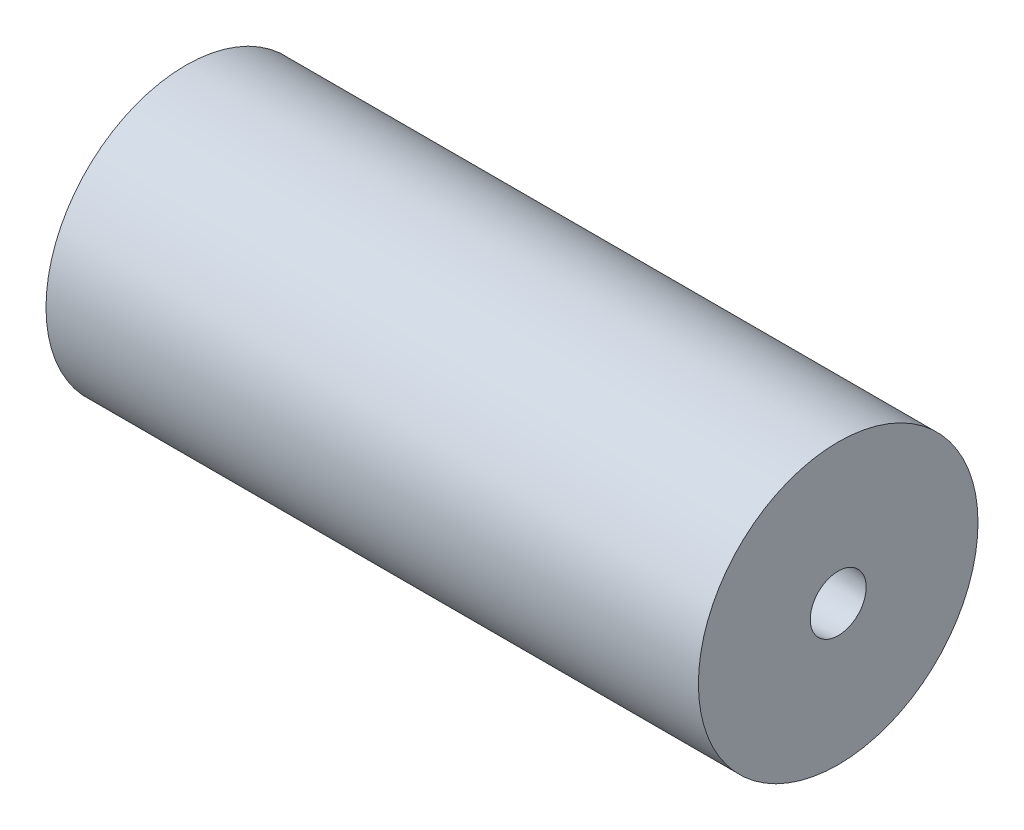
SolidWorks part; units mm, degrees
ref_plane "Front Plane" through (0, 0, 0) normal (0, 0, 1) x (1, 0, 0)
ref_plane "Top Plane" through (0, 0, 0) normal (0, 1, 0) x (1, 0, 0)
ref_plane "Right Plane" through (0, 0, 0) normal (1, 0, 0) x (0, 0, -1)
sketch "Sketch1" plane through (0, 0, 0) normal (0, 0, 1) x (1, 0, 0)
  line L0 (-22.225, 9.525) -> (-22.225, 5.0132)
  line L1 (-22.225, 0) -> (22.225, 0) construction
  line L3 (-22.225, 9.525) -> (22.225, 9.525)
  line L4 (22.225, 1.905) -> (22.225, 9.525)
  line L6 (-22.225, 5.0132) -> (22.225, 1.905)
  point P4 (0, 9.525)
  point P7 (0, 0)
  dimension "D1" = 3.81
  dimension "D2" = 19.05
  dimension "D3" = 44.45
  dimension "D4" = 4
revolve "Revolve1" add sketch "Sketch1" angle 360 about L1
